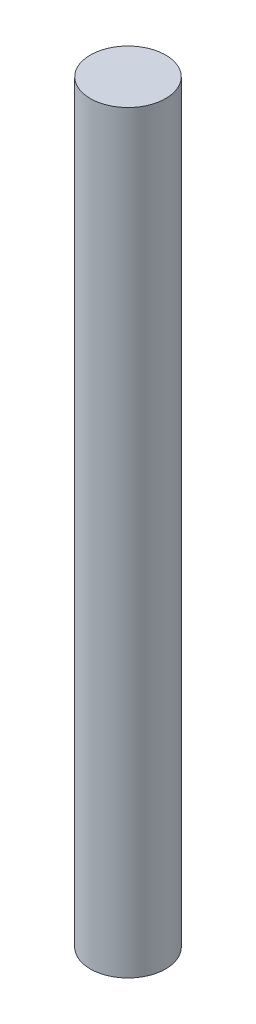
SolidWorks part; units mm, degrees
ref_plane "Front Plane" through (0, 0, 0) normal (0, 0, 1) x (1, 0, 0)
ref_plane "Top Plane" through (0, 0, 0) normal (0, 1, 0) x (1, 0, 0)
ref_plane "Right Plane" through (0, 0, 0) normal (1, 0, 0) x (0, 0, -1)
sketch "Sketch1" plane through (0, 0, 0) normal (0, 1, 0) x (1, 0, 0)
  circle A0 centre (-4.4377, -4.5419) radius 6.35
  dimension "D1" = 12.7
extrude "Boss-Extrude1" add sketch "Sketch1" along normal blind 127
